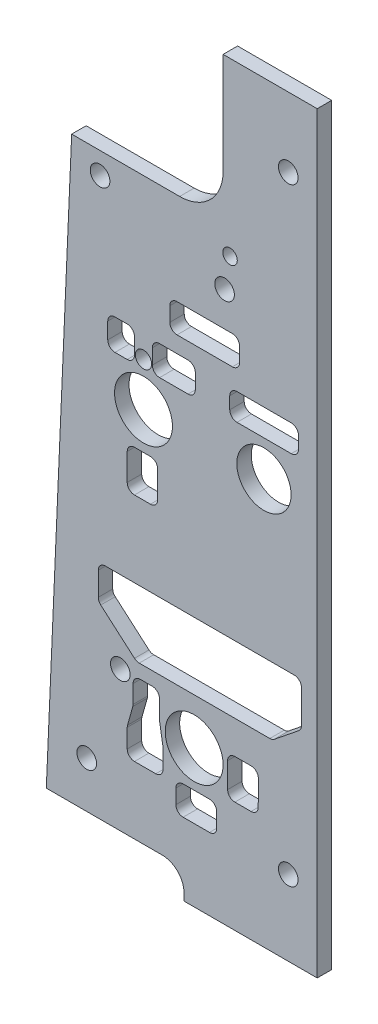
SolidWorks part; units mm, degrees
material "Acrylic (Medium-high impact)"
ref_plane "Front Plane" through (0, 0, 0) normal (0, 0, 1) x (1, 0, 0)
ref_plane "Top Plane" through (0, 0, 0) normal (0, 1, 0) x (1, 0, 0)
ref_plane "Right Plane" through (0, 0, 0) normal (1, 0, 0) x (0, 0, -1)
sketch "Sketch1" plane through (0, 0, 0) normal (0, 0, 1) x (1, 0, 0)
  line L8 (-29.21, 1.5875) -> (-29.21, 0)
  line L9 (-29.21, 0) -> (0, 0)
  line L10 (0, 0) -> (0, 165.1)
  line L11 (0, 165.1) -> (-25.4, 165.1)
  line L12 (-25.4, 165.1) -> (-25.4, 138.1125)
  line L13 (-30.1625, 133.35) -> (-53.848, 133.35)
  line L14 (-53.848, 133.35) -> (-59.4118, 6.35)
  line L15 (-59.4118, 6.35) -> (-33.9725, 6.35)
  line L16 (-29.21, 1.5875) -> (-29.21, 0)
  line L17 (-29.21, 0) -> (0, 0)
  line L18 (0, 0) -> (0, 165.1)
  line L19 (0, 165.1) -> (-25.4, 165.1)
  line L20 (-25.4, 165.1) -> (-25.4, 138.1125)
  line L21 (-30.1625, 133.35) -> (-53.848, 133.35)
  line L22 (-53.848, 133.35) -> (-59.4118, 6.35)
  line L23 (-59.4118, 6.35) -> (-33.9725, 6.35)
  arc A2 (-29.21, 1.5875) -> (-33.9725, 6.35) centre (-33.9725, 1.5875) ccw
  arc A3 (-30.1625, 133.35) -> (-25.4, 138.1125) centre (-30.1625, 138.1125) ccw
  arc A4 (-29.21, 1.5875) -> (-33.9725, 6.35) centre (-33.9725, 1.5875) ccw
  arc A5 (-30.1625, 133.35) -> (-25.4, 138.1125) centre (-30.1625, 138.1125) ccw
  dimension "D1" = 0
extrude "Boss-Extrude1" add sketch "Sketch1" against normal blind 3.175
hole_wizard "#6 Clearance Hole1" positions "Sketch3" profile "Sketch2" hole size "#6" standard "ANSI Inch" end condition through all
sketch "Sketch3" plane through (0, 0, 0) normal (0, 0, 1) x (1, 0, 0)
  point P0 (-47.625, 128.5875)
  point P3 (-6.35, 149.86)
  point P6 (-50.546, 16.51)
  point P9 (-6.35, 16.51)
sketch "Sketch2" plane through (-47.625, 128.5875, 0) normal (1, 0, 0) x (0, -1, 0)
  line L0 (0, 0) -> (0, 3.175)
  line L1 (0, 3.175) -> (2.1526, 3.175)
  line L2 (2.1526, 3.175) -> (2.1526, 0)
  line L5 (2.1526, 0) -> (0, 0)
  line L11 (0, -6.35) -> (0, 107.95) construction
  dimension "Thru Hole Dia." = 4.3053
  dimension "Thru Hole Depth" = 3.175
hole_wizard "#6 Clearance Hole2" positions "Sketch5" profile "Sketch4" hole size "#6" standard "ANSI Inch" end condition through all
sketch "Sketch5" plane through (0, 0, 0) normal (0, 0, 1) x (1, 0, 0)
  point P0 (-43.18, 37.084)
  point P3 (-20.32, 120.65)
sketch "Sketch4" plane through (-43.18, 37.084, 0) normal (1, 0, 0) x (0, -1, 0)
  line L0 (0, 0) -> (0, 3.175)
  line L1 (0, 3.175) -> (2.1526, 3.175)
  line L2 (2.1526, 3.175) -> (2.1526, 0)
  line L5 (2.1526, 0) -> (0, 0)
  line L11 (0, -6.35) -> (0, 107.95) construction
  dimension "Thru Hole Dia." = 4.3053
  dimension "Thru Hole Depth" = 3.175
hole_wizard "9/64 (0.14063) Diameter Hole1" positions "Sketch7" profile "Sketch6" hole size "9/64" standard "ANSI Inch" end condition through all
sketch "Sketch7" plane through (0, 0, 0) normal (0, 0, 1) x (1, 0, 0)
  point P0 (-38.1, 98.425)
  point P3 (-36.5125, 30.1625)
sketch "Sketch6" plane through (-38.1, 98.425, 0) normal (1, 0, 0) x (0, -1, 0)
  line L0 (0, 0) -> (0, 3.175)
  line L1 (0, 3.175) -> (1.786, 3.175)
  line L2 (1.786, 3.175) -> (1.786, 0)
  line L5 (1.786, 0) -> (0, 0)
  line L11 (0, -6.35) -> (0, 107.95) construction
  dimension "Thru Hole Dia." = 3.572
  dimension "Thru Hole Depth" = 3.175
hole_wizard "15/32 (0.46875) Diameter Hole1" positions "Sketch9" profile "Sketch8" hole size "15/32" standard "ANSI Inch" end condition through all
sketch "Sketch9" plane through (0, 0, 0) normal (0, 0, 1) x (1, 0, 0)
  point P0 (-11.684, 88.9)
sketch "Sketch8" plane through (-11.684, 88.9, 0) normal (1, 0, 0) x (0, -1, 0)
  line L0 (0, 0) -> (0, 3.175)
  line L1 (0, 3.175) -> (5.9531, 3.175)
  line L2 (5.9531, 3.175) -> (5.9531, 0)
  line L5 (5.9531, 0) -> (0, 0)
  line L11 (0, -6.35) -> (0, 107.95) construction
  dimension "Thru Hole Dia." = 11.9062
  dimension "Thru Hole Depth" = 3.175
hole_wizard "1/2 (0.5) Diameter Hole1" positions "Sketch11" profile "Sketch10" hole size "1/2" standard "ANSI Inch" end condition through all
sketch "Sketch11" plane through (0, 0, 0) normal (0, 0, 1) x (1, 0, 0)
  point P0 (-38.1, 88.9)
  point P3 (-26.9875, 30.1625)
sketch "Sketch10" plane through (-38.1, 88.9, 0) normal (1, 0, 0) x (0, -1, 0)
  line L0 (0, 0) -> (0, 3.175)
  line L1 (0, 3.175) -> (6.35, 3.175)
  line L2 (6.35, 3.175) -> (6.35, 0)
  line L5 (6.35, 0) -> (0, 0)
  line L11 (0, -6.35) -> (0, 107.95) construction
  dimension "Thru Hole Dia." = 12.7
  dimension "Thru Hole Depth" = 3.175
sketch "Sketch12" plane through (0, 0, 0) normal (0, 0, 1) x (1, 0, 0)
  line L0 (0, 165.1) -> (-25.4, 165.1) construction
  line L1 (-20.6375, 165.1) -> (-30.1625, 165.1)
  line L2 (-20.6375, 165.1) -> (-20.6375, 133.35)
  line L3 (-20.6375, 133.35) -> (-30.1625, 133.35)
  line L4 (-30.1625, 165.1) -> (-30.1625, 133.35)
  line L5 (-25.4, 165.1) -> (-25.4, 138.1125) construction
  dimension "D1" = 4.7625
extrude "Cut-Extrude1" cut sketch "Sketch12" against normal up to next
fillet "Fillet1" radius 9.525 1 edges at (-20.6375, 133.35, -1.5875)
sketch "Sketch13" plane through (0, 0, 0) normal (0, 0, 1) x (1, 0, 0)
  line L0 (-30.7478, 113.0864) -> (-18.616, 113.0864)
  line L1 (-17.0285, 111.4989) -> (-17.0285, 108.3583)
  line L2 (-18.616, 106.7708) -> (-30.7478, 106.7708)
  line L3 (-32.3353, 108.3583) -> (-32.3353, 111.4989)
  line L4 (-34.5742, 103.1949) -> (-28.3255, 103.1949)
  line L5 (-26.738, 101.6074) -> (-26.738, 98.3259)
  line L6 (-28.3255, 96.7384) -> (-34.5742, 96.7384)
  line L7 (-36.1617, 98.3259) -> (-36.1617, 101.6074)
  line L8 (-40.0808, 98.225) -> (-40.0808, 101.7856)
  line L9 (-41.6683, 103.3731) -> (-44.3528, 103.3731)
  line L10 (-45.9403, 101.7856) -> (-45.9403, 98.225)
  line L11 (-44.3528, 96.6375) -> (-41.6683, 96.6375)
  line L12 (-40.0808, 80.7593) -> (-36.5751, 80.7593)
  line L13 (-34.9876, 79.1718) -> (-34.9876, 73.2877)
  line L14 (-36.5751, 71.7002) -> (-40.0808, 71.7002)
  line L15 (-41.6683, 73.2877) -> (-41.6683, 79.1718)
  line L16 (-17.5944, 102.5821) -> (-5.696, 102.5821)
  line L17 (-4.1085, 100.9946) -> (-4.1085, 98.3259)
  line L18 (-5.696, 96.7384) -> (-17.5944, 96.7384)
  line L19 (-19.1819, 98.3259) -> (-19.1819, 100.9946)
  line L20 (-48.0191, 53.4281) -> (-48.0191, 48.2949)
  line L21 (-47.4716, 47.0956) -> (-40.0723, 40.6793)
  line L22 (-39.0322, 40.2911) -> (-10.3944, 40.2911)
  line L23 (-9.3988, 40.6421) -> (-4.0444, 44.953)
  line L24 (-3.4525, 46.1896) -> (-3.4525, 53.4281)
  line L25 (-5.04, 55.0156) -> (-46.4316, 55.0156)
  line L26 (-40.3845, 35.7367) -> (-40.3845, 31.7652)
  line L28 (-34.5742, 31.6755) -> (-34.5742, 35.7367)
  line L29 (-36.1617, 37.3242) -> (-38.797, 37.3242)
  line L31 (-33.8284, 26.8634) -> (-33.8284, 22.6726)
  line L32 (-35.4159, 21.0851) -> (-40.0766, 21.0851)
  line L33 (-41.6641, 22.6726) -> (-41.6641, 26.7737)
  line L34 (-29.4065, 22.1594) -> (-23.6235, 22.1594)
  line L35 (-22.036, 20.5719) -> (-22.036, 17.4274)
  line L36 (-23.6235, 15.8399) -> (-29.4065, 15.8399)
  line L37 (-30.994, 17.4274) -> (-30.994, 20.5719)
  line L38 (-19.6522, 31.4531) -> (-19.6522, 25.9613)
  line L39 (-18.0647, 24.3738) -> (-14.5239, 24.3738)
  line L40 (-12.9364, 25.953) -> (-12.9075, 31.4447)
  line L42 (-14.4949, 33.0406) -> (-18.0647, 33.0406)
  line L44 (-40.4437, 31.3357) -> (-41.6049, 27.2032)
  line L45 (-34.5533, 31.4189) -> (-33.8493, 27.12)
  arc A0 (-18.616, 113.0864) -> (-17.0285, 111.4989) centre (-18.616, 111.4989) cw
  arc A1 (-17.0285, 108.3583) -> (-18.616, 106.7708) centre (-18.616, 108.3583) cw
  arc A2 (-30.7478, 106.7708) -> (-32.3353, 108.3583) centre (-30.7478, 108.3583) cw
  arc A3 (-30.7478, 113.0864) -> (-32.3353, 111.4989) centre (-30.7478, 111.4989) ccw
  arc A5 (-34.5742, 96.7384) -> (-36.1617, 98.3259) centre (-34.5742, 98.3259) cw
  arc A6 (-26.738, 98.3259) -> (-28.3255, 96.7384) centre (-28.3255, 98.3259) cw
  arc A7 (-28.3255, 103.1949) -> (-26.738, 101.6074) centre (-28.3255, 101.6074) cw
  arc A8 (-36.1617, 101.6074) -> (-34.5742, 103.1949) centre (-34.5742, 101.6074) cw
  arc A9 (-40.0808, 101.7856) -> (-41.6683, 103.3731) centre (-41.6683, 101.7856) ccw
  arc A10 (-45.9403, 98.225) -> (-44.3528, 96.6375) centre (-44.3528, 98.225) ccw
  arc A11 (-44.3528, 103.3731) -> (-45.9403, 101.7856) centre (-44.3528, 101.7856) ccw
  arc A12 (-40.0808, 98.225) -> (-41.6683, 96.6375) centre (-41.6683, 98.225) cw
  arc A13 (-40.0808, 71.7002) -> (-41.6683, 73.2877) centre (-40.0808, 73.2877) cw
  arc A14 (-34.9876, 73.2877) -> (-36.5751, 71.7002) centre (-36.5751, 73.2877) cw
  arc A15 (-36.5751, 80.7593) -> (-34.9876, 79.1718) centre (-36.5751, 79.1718) cw
  arc A16 (-40.0808, 80.7593) -> (-41.6683, 79.1718) centre (-40.0808, 79.1718) ccw
  arc A17 (-5.696, 102.5821) -> (-4.1085, 100.9946) centre (-5.696, 100.9946) cw
  arc A18 (-4.1085, 98.3259) -> (-5.696, 96.7384) centre (-5.696, 98.3259) cw
  arc A19 (-17.5944, 96.7384) -> (-19.1819, 98.3259) centre (-17.5944, 98.3259) cw
  arc A20 (-17.5944, 102.5821) -> (-19.1819, 100.9946) centre (-17.5944, 100.9946) ccw
  arc A21 (-3.4525, 53.4281) -> (-5.04, 55.0156) centre (-5.04, 53.4281) ccw
  arc A22 (-4.0444, 44.953) -> (-3.4525, 46.1896) centre (-5.04, 46.1896) ccw
  arc A23 (-10.3944, 40.2911) -> (-9.3988, 40.6421) centre (-10.3944, 41.8786) ccw
  arc A24 (-48.0191, 48.2949) -> (-47.4716, 47.0956) centre (-46.4316, 48.2949) ccw
  arc A25 (-40.0723, 40.6793) -> (-39.0322, 40.2911) centre (-39.0322, 41.8786) ccw
  arc A26 (-48.0191, 53.4281) -> (-46.4316, 55.0156) centre (-46.4316, 53.4281) cw
  arc A27 (-34.5742, 35.7367) -> (-36.1617, 37.3242) centre (-36.1617, 35.7367) ccw
  arc A30 (-40.3845, 35.7367) -> (-38.797, 37.3242) centre (-38.797, 35.7367) cw
  arc A31 (-40.0766, 21.0851) -> (-41.6641, 22.6726) centre (-40.0766, 22.6726) cw
  arc A32 (-33.8284, 22.6726) -> (-35.4159, 21.0851) centre (-35.4159, 22.6726) cw
  arc A35 (-29.4065, 15.8399) -> (-30.994, 17.4274) centre (-29.4065, 17.4274) cw
  arc A36 (-22.036, 17.4274) -> (-23.6235, 15.8399) centre (-23.6235, 17.4274) cw
  arc A37 (-23.6235, 22.1594) -> (-22.036, 20.5719) centre (-23.6235, 20.5719) cw
  arc A38 (-29.4065, 22.1594) -> (-30.994, 20.5719) centre (-29.4065, 20.5719) ccw
  arc A39 (-12.9075, 31.4447) -> (-14.4949, 33.0406) centre (-14.4949, 31.4531) ccw
  arc A40 (-14.5239, 24.3738) -> (-12.9364, 25.953) centre (-14.5239, 25.9613) ccw
  arc A41 (-19.6522, 25.9613) -> (-18.0647, 24.3738) centre (-18.0647, 25.9613) ccw
  arc A42 (-19.6522, 31.4531) -> (-18.0647, 33.0406) centre (-18.0647, 31.4531) cw
  circle A43 centre (-19.1196, 127.4983) radius 1.5875
  arc A44 (-34.5742, 31.6755) -> (-34.5533, 31.4189) centre (-32.9867, 31.6755) ccw
  arc A45 (-33.8284, 26.8634) -> (-33.8493, 27.12) centre (-35.4159, 26.8634) ccw
  arc A46 (-41.6641, 26.7737) -> (-41.6049, 27.2032) centre (-40.0766, 26.7737) cw
  arc A47 (-40.3845, 31.7652) -> (-40.4437, 31.3357) centre (-41.972, 31.7652) cw
  point P122 (-12.899, 33.0406)
  dimension "D1" = 1.5875
  dimension "D2" = 1.5875
  dimension "D3" = 1.5875
  dimension "D4" = 1.5875
  dimension "D5" = 1.5875
  dimension "D6" = 1.5875
  dimension "D7" = 1.5875
  dimension "D8" = 1.5875
  dimension "D9" = 1.5875
  dimension "D10" = 1.5875
  dimension "D11" = 1.5875
extrude "Cut-Extrude2" cut sketch "Sketch13" against normal through all
